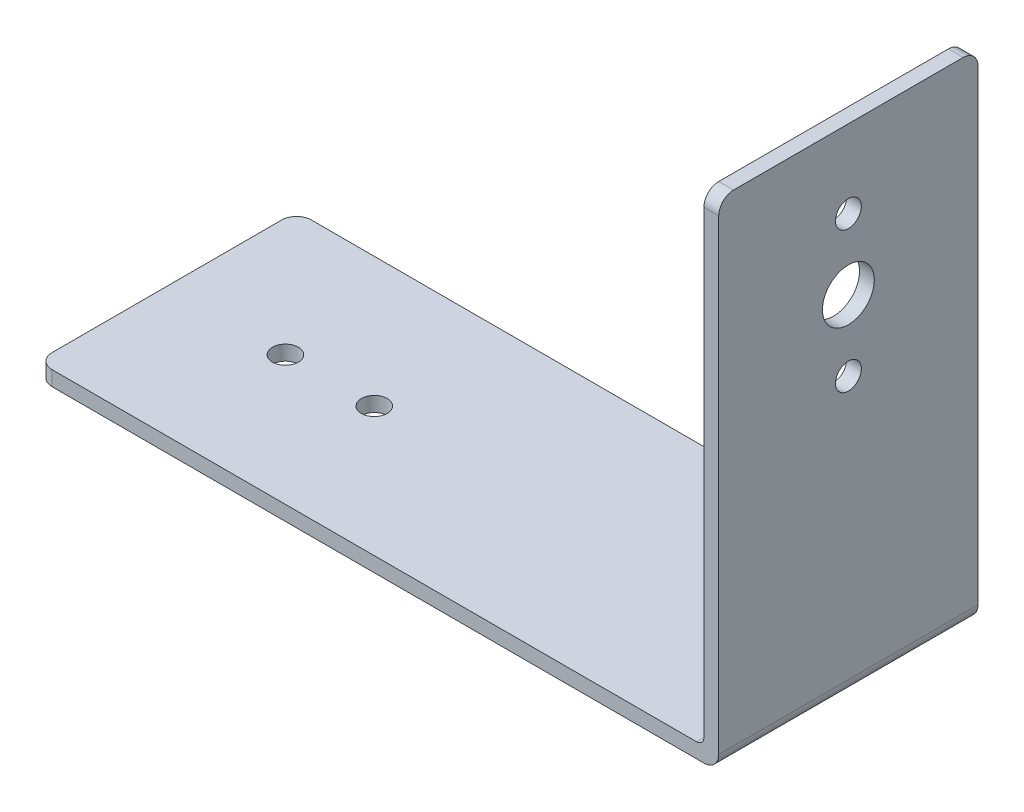
SolidWorks part; units mm, degrees
material "Alliage 2024"
ref_plane "Plan de face" through (0, 0, 0) normal (0, 0, 1) x (1, 0, 0)
ref_plane "Plan de dessus" through (0, 0, 0) normal (0, 1, 0) x (1, 0, 0)
ref_plane "Plan de droite" through (0, 0, 0) normal (1, 0, 0) x (0, 0, -1)
sketch "Esquisse1" plane through (0, 0, 0) normal (0, 0, 1) x (1, 0, 0)
  line L0 (0, 0) -> (90, 0)
  line L1 (90, 0) -> (90, 65)
  dimension "D1" = 0
  dimension "D3" = 90
  dimension "D4" = 65
extrude "Extru.-Mince1" add sketch "Esquisse1" along normal blind 35 thin contours L0 L1 thin type one direction wall 2
fillet "Congé1" radius 2 1 edges at (92, -2, 17.5)
fillet "Congé3" radius 1 1 edges at (90, 0, 17.5)
sketch "Esquisse3" plane through (92, 0, 0) normal (1, 0, 0) x (0, 0, -1)
  line L0 (-17.5, 34.095) -> (-17.5, 61.4768) construction
  line L1 (-30.3181, 45) -> (10.1, 45) construction
  line L2 (-35, 0) -> (-35, 65) construction
  line L3 (-35, 65) -> (0, 65) construction
  circle A0 centre (-17.5, 35.5) radius 1.75
  circle A1 centre (-17.5, 54.5) radius 1.75
  circle A4 centre (-17.5, 45) radius 3.5
  dimension "D2" = 20
  dimension "D3" = 9.5
  dimension "D4" = 9.5
  dimension "D5" = 3.5
  dimension "D8" = 3.5
  dimension "D11" = 7
  dimension "D1" = 17.5
extrude "Enlèv. mat.-Extru.2" cut sketch "Esquisse3" against normal blind 2
fillet "Congé5" radius 2 1 edges at (91, 65, 35)
fillet "Congé6" radius 2 1 edges at (91, 65, 0)
fillet "Congé7" radius 2 1 edges at (0, -1, 0)
fillet "Congé8" radius 2 1 edges at (0, -1, 35)
sketch "Esquisse4" plane through (0, 0, 0) normal (0, 1, 0) x (1, 0, 0)
  line L0 (22, 6.8371) -> (22, -34.2545) construction
  line L1 (29.5005, -17.5) -> (81.1492, -17.5) construction
  line L2 (2, 0) -> (89, 0) construction
  line L3 (92, -33) -> (92, -2) construction
  circle A2 centre (28, -17.5) radius 1.75
  circle A3 centre (16, -17.5) radius 1.75
  dimension "D3" = 3.5
  dimension "D6" = 3.5
  dimension "D1" = 17.5
  dimension "D2" = 6
  dimension "D9" = 70
  dimension "D10" = 6
extrude "Enlèv. mat.-Extru.3" cut sketch "Esquisse4" against normal blind 2
